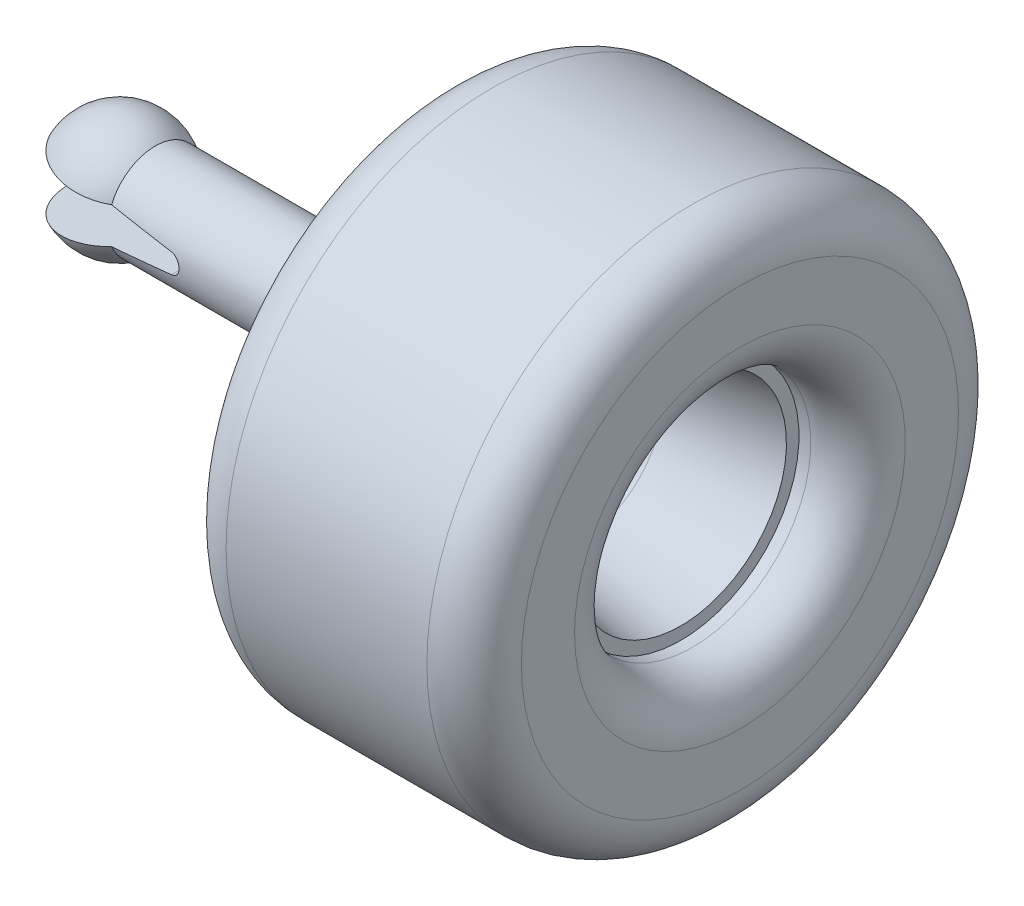
SolidWorks part; units mm, degrees
ref_plane "前基準面" through (0, 0, 0) normal (0, 0, 1) x (1, 0, 0)
ref_plane "上基準面" through (0, 0, 0) normal (0, 1, 0) x (1, 0, 0)
ref_plane "右基準面" through (0, 0, 0) normal (1, 0, 0) x (0, 0, -1)
sketch "草圖1" plane through (0, 0, 0) normal (0, 0, 1) x (1, 0, 0)
  line L0 (0, 0) -> (105, 0) construction
  line L1 (6, 8) -> (49, 8)
  line L2 (55, 14) -> (55, 37)
  line L3 (63, 45) -> (97, 45)
  line L4 (105, 37) -> (105, 28)
  line L5 (95, 20) -> (97, 20)
  line L6 (95, 20) -> (95, 17.8763)
  line L7 (66.1557, 5.7738) -> (75, 5)
  line L8 (75, 5) -> (75, 0)
  line L9 (77.3953, 14.7721) -> (95, 17.8763)
  line L10 (-10, 0) -> (75, 0)
  arc A0 (6, 8) -> (-10, 0) centre (0, 0) ccw
  arc A1 (49, 8) -> (55, 14) centre (49, 14) ccw
  arc A2 (55, 37) -> (63, 45) centre (63, 37) cw
  arc A3 (105, 28) -> (97, 20) centre (97, 28) cw
  arc A4 (105, 37) -> (97, 45) centre (97, 37) ccw
  arc A5 (77.3953, 14.7721) -> (66.1557, 5.7738) centre (80, 0) ccw
  dimension "D2" = 10
  dimension "D4" = 6
  dimension "D5" = 8
  dimension "D6" = 8
  dimension "D13" = 15
  dimension "D16" = 105
  dimension "D3" = 16
  dimension "D7" = 90
  dimension "D8" = 40
  dimension "D9" = 50
  dimension "D10" = 5
  dimension "D11" = 5
  dimension "D12" = 10
  dimension "D14" = 10
  dimension "D15" = 20
  dimension "D17" = 25
revolve "旋轉1" add sketch "草圖1" angle 360 about L0
sketch "草圖2" plane through (0, 0, 0) normal (0, 0, 1) x (1, 0, 0)
  line L0 (-8.6603, 5) -> (16.5609, 1.6796)
  line L1 (-10, 0) -> (75, 0) construction
  line L2 (-13.201, 0) -> (25.5444, 0) construction
  line L3 (-8.6603, -5) -> (16.5609, -1.6796)
  arc A0 (6, 8) -> (-10, 0) centre (0, 0) ccw construction
  arc A1 (16.5609, 1.6796) -> (16.5609, -1.6796) centre (16.3397, 0) cw
  dimension "D1" = 10
  dimension "D2" = 15
  dimension "D3" = 25
extrude "除料-伸長1" cut sketch "草圖2" against normal through all and the other way through all
